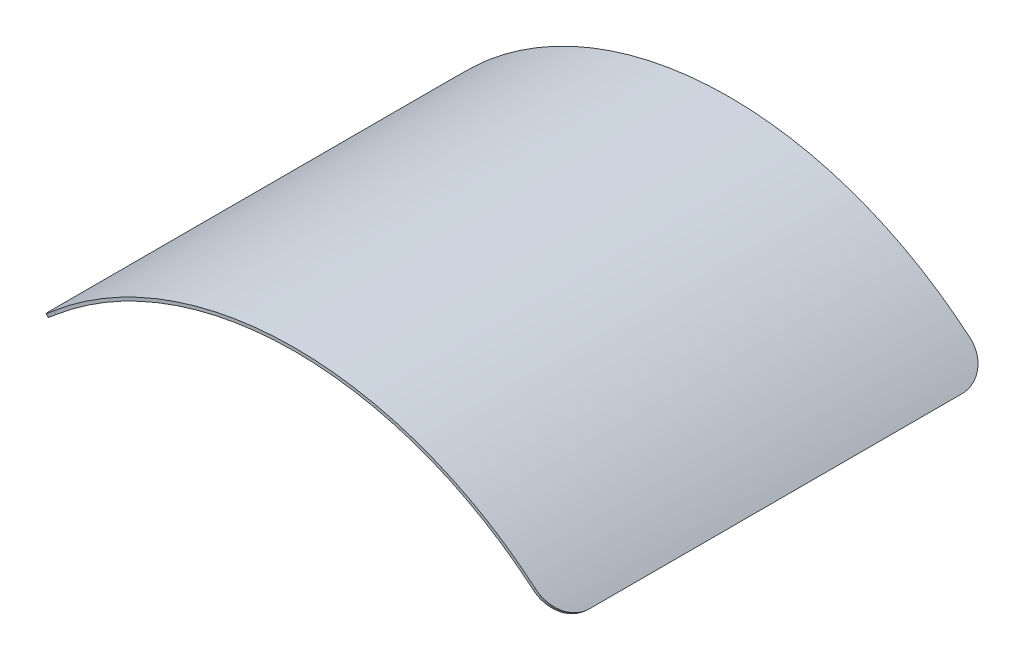
SolidWorks part; units mm, degrees
ref_plane "Front Plane" through (0, 0, 0) normal (0, 0, 1) x (1, 0, 0)
ref_plane "Top Plane" through (0, 0, 0) normal (0, 1, 0) x (1, 0, 0)
ref_plane "Right Plane" through (0, 0, 0) normal (1, 0, 0) x (0, 0, -1)
sketch "Sketch1" plane through (0, 0, 0) normal (0, 0, 1) x (1, 0, 0)
  line L5 (1700, 0) -> (1692.4771, -6.6179)
  line L6 (7.0833, -7.0588) -> (0, 0)
  line L7 (1700, 0) -> (1789.9389, -116.1111) construction
  line L8 (1692.4771, -6.6179) -> (1782.0332, -122.2348) construction
  arc A0 (0, 0) -> (1700, 0) centre (850, -847.0537) cw
  arc A1 (7.0833, -7.0588) -> (1692.4771, -6.6179) centre (850, -847.0537) cw
  point P9 (0, 0)
  dimension "D1" = 1200
  dimension "D2" = 1700
  dimension "D4" = 10
extrude "Boss-Extrude1" add sketch "Sketch1" along normal blind 1400 contours A0 L5 A1 L6
fillet "Fillet1" radius 100 3 edges at (1696.2386, -3.309, 0) (3.5417, -3.5294, 0) (3.5417, -3.5294, 1400)
fillet "Fillet2" radius 100 1 edges at (1696.2386, -3.309, 1400)
